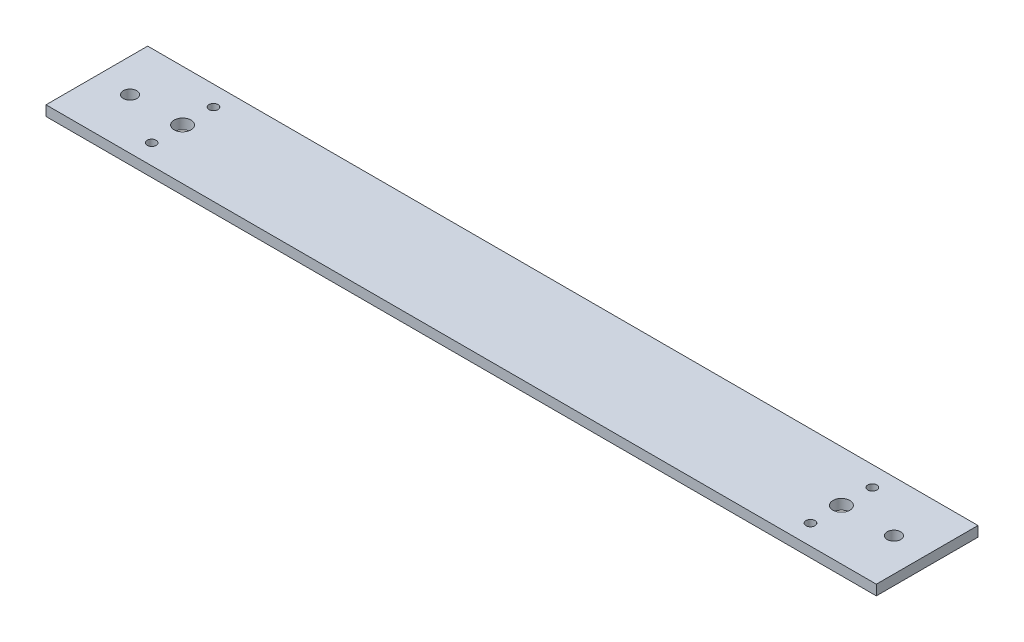
SolidWorks part; units mm, degrees
material "Maple"
ref_plane "Front Plane" through (0, 0, 0) normal (0, 0, 1) x (1, 0, 0)
ref_plane "Top Plane" through (0, 0, 0) normal (0, 1, 0) x (1, 0, 0)
ref_plane "Right Plane" through (0, 0, 0) normal (1, 0, 0) x (0, 0, -1)
sketch "Sketch2" plane through (0, 0, 0) normal (0, 1, 0) x (1, 0, 0)
  line L1 (-245, 30) -> (245, 30)
  line L2 (-245, 30) -> (-245, -30)
  line L3 (-245, -30) -> (245, -30)
  line L4 (245, 30) -> (245, -30)
  line L5 (-245, 30) -> (245, -30) construction
  line L6 (-245, -30) -> (245, 30) construction
  point P0 (0, 0)
  dimension "D1" = 490
  dimension "D2" = 60
extrude "Boss-Extrude1" add sketch "Sketch2" along normal blind 6
ref_plane "Plane1" through (0, 3, 0) normal (0, 1, 0) x (1, 0, 0)
hole_wizard "Ø10.0 (10) Diameter Hole1" positions "Sketch4" profile "Sketch3" hole size "Ø10.0" standard "ANSI Metric" end condition through all
sketch "Sketch4" plane through (0, 6, 0) normal (0, 1, 0) x (1, 0, 0)
  circle A0 centre (194.4, 0) radius 4 construction
  point P0 (194.4, 0)
sketch "Sketch3" plane through (194.4, 6, 0) normal (1, 0, 0) x (0, 0, 1)
  line L0 (0, 0) -> (0, 6)
  line L1 (0, 6) -> (5, 6)
  line L2 (5, 6) -> (5, 0)
  line L5 (5, 0) -> (0, 0)
  line L11 (0, -6.35) -> (0, 107.95) construction
  dimension "Thru Hole Dia." = 10
  dimension "Thru Hole Depth" = 6
hole_wizard "M5 Clearance Hole1" positions "Sketch6" profile "Sketch5" hole size "M5" standard "ANSI Metric" end condition through all
sketch "Sketch6" plane through (0, 6, 0) normal (0, 1, 0) x (1, 0, 0)
  circle A0 centre (194.4, 18.25) radius 2.65 construction
  circle A1 centre (194.4, -18.25) radius 2.65 construction
  point P0 (194.4, -18.25)
  point P2 (194.4, 18.25)
sketch "Sketch5" plane through (194.4, 6, 18.25) normal (1, 0, 0) x (0, 0, 1)
  line L0 (0, 0) -> (0, 6)
  line L1 (0, 6) -> (2.65, 6)
  line L2 (2.65, 6) -> (2.65, 0)
  line L5 (2.65, 0) -> (0, 0)
  line L11 (0, -6.35) -> (0, 107.95) construction
  dimension "Thru Hole Dia." = 5.3
  dimension "Thru Hole Depth" = 6
hole_wizard "Ø8.0 (8) Diameter Hole1" positions "Sketch8" profile "Sketch7" hole size "Ø8.0" standard "ANSI Metric" end condition through all
sketch "Sketch8" plane through (0, 6, 0) normal (0, 1, 0) x (1, 0, 0)
  point P0 (225.4, 0)
sketch "Sketch7" plane through (225.4, 6, 0) normal (1, 0, 0) x (0, 0, 1)
  line L0 (0, 0) -> (0, 6)
  line L1 (0, 6) -> (4, 6)
  line L2 (4, 6) -> (4, 0)
  line L5 (4, 0) -> (0, 0)
  line L11 (0, -6.35) -> (0, 107.95) construction
  dimension "Thru Hole Dia." = 8
  dimension "Thru Hole Depth" = 6
mirror "Mirror1" about plane through (0, 0, 0) normal (1, 0, 0) of "Ø8.0 (8) Diameter Hole1", "Ø10.0 (10) Diameter Hole1", "M5 Clearance Hole1"
